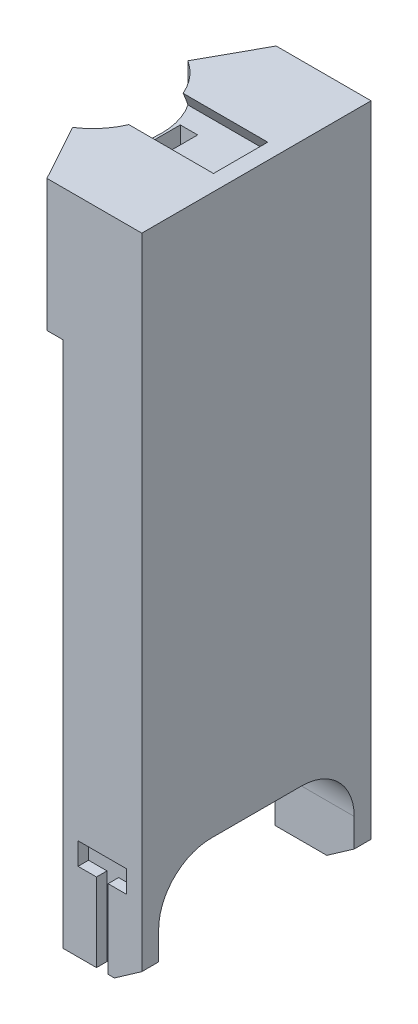
SolidWorks part; units mm, degrees
ref_plane "Front Plane" through (0, 0, 0) normal (0, 0, 1) x (1, 0, 0)
ref_plane "Top Plane" through (0, 0, 0) normal (0, 1, 0) x (1, 0, 0)
ref_plane "Right Plane" through (0, 0, 0) normal (1, 0, 0) x (0, 0, -1)
sketch "Sketch2" plane through (0, 0, 0) normal (0, 1, 0) x (1, 0, 0)
  line L0 (-9, 21.75) -> (-14.9513, 10.9504)
  line L1 (-9, -21.75) -> (9, -21.75)
  line L2 (-9, -21.75) -> (-9, 21.75)
  line L3 (-9, 21.75) -> (9, 21.75)
  line L4 (9, -21.75) -> (9, 21.75)
  line L5 (-9, -21.75) -> (9, 21.75) construction
  line L6 (-9, 21.75) -> (9, -21.75) construction
  line L7 (-9, -21.75) -> (-14.9513, -10.9504)
  circle A0 centre (-22.05, 0) radius 13.05
  point P0 (0, 0)
  point P8 (0, 0)
  point P11 (-27.9421, 0)
  point P12 (-15.3434, 15.5108)
  point P13 (-16.5401, 11.8298)
  point P14 (0, 0)
  point P15 (-14.9513, 10.9504)
  dimension "D1" = 26.1
  dimension "D2" = 43.5
  dimension "D3" = 18
extrude "Boss-Extrude1" add sketch "Sketch2" along normal blind 25 contours A0 L2 L0 | A0 L7 L2 | L1 L4 L3 L2 region at (-10.8717, 0, -12.2283) region at (0, 0, 0) region at (-10.8717, 0, 12.2283)
ref_plane "Plane1" through (-9, 0, 0) normal (1, 0, 0) x (0, 0, -1)
sketch "Sketch3" plane through (-9, 0, 0) normal (1, 0, 0) x (0, 0, -1)
  line L0 (-5.15, 25) -> (5.15, 25)
  line L1 (5.15, 25) -> (7.15, 21.5359)
  line L2 (7.15, 21.5359) -> (-7.15, 21.5359)
  line L3 (-7.15, 21.5359) -> (-5.15, 25)
  line L4 (-21.75, 25) -> (21.75, 25) construction
  point P4 (0, 25)
  point P7 (0, 25)
  point P8 (0, 21.5359)
  dimension "D1" = 10.3
  dimension "D2" = 14.3
  dimension "D3" = 60
extrude "Cut-Extrude1" cut sketch "Sketch3" against normal through all and the other way blind 15
sketch "Sketch4" plane through (-9, 0, 0) normal (1, 0, 0) x (0, 0, -1)
  line L0 (0, 29.4041) -> (0, 4.5359) construction
  line L1 (3.15, 29.4041) -> (3.15, 4.5359)
  line L2 (-3.15, 29.4041) -> (-3.15, 4.5359)
  line L3 (7.15, 21.5359) -> (-7.15, 21.5359) construction
  arc A0 (3.15, 29.4041) -> (-3.15, 29.4041) centre (0, 29.4041) ccw
  arc A1 (-3.15, 4.5359) -> (3.15, 4.5359) centre (0, 4.5359) ccw
  point P3 (0, 16.97)
  dimension "D1" = 6.3
  dimension "D2" = 17
extrude "Cut-Extrude2" cut sketch "Sketch4" along normal blind 3.3 from offset 0.4
sketch "Sketch5" plane through (0, 0, 0) normal (0, -1, 0) x (1, 0, 0)
  line L0 (-9, -21.75) -> (9, -21.75) construction
  line L1 (9, 21.75) -> (-6, 21.75)
  line L2 (9, 21.75) -> (9, -21.75)
  line L3 (9, -21.75) -> (-6, -21.75)
  line L4 (-6, 21.75) -> (-6, -21.75)
  dimension "D1" = 15
extrude "Boss-Extrude2" add sketch "Sketch5" along normal blind 100
sketch "Sketch6" plane through (0, 0, 21.75) normal (0, 0, 1) x (1, 0, 0)
  line L1 (0.4, -85.1) -> (2.6, -85.1)
  line L2 (0.4, -85.1) -> (0.4, -100)
  line L3 (0.4, -100) -> (2.6, -100)
  line L4 (2.6, -85.1) -> (2.6, -100)
  line L5 (0.4, -85.1) -> (2.6, -100) construction
  line L6 (0.4, -100) -> (2.6, -85.1) construction
  line L7 (9, -100) -> (-6, -100) construction
  line L8 (-3.1, -80.9) -> (6.1, -80.9)
  line L9 (-3.1, -80.9) -> (-3.1, -85.1)
  line L10 (-3.1, -85.1) -> (6.1, -85.1)
  line L11 (6.1, -80.9) -> (6.1, -85.1)
  line L12 (-3.1, -80.9) -> (6.1, -85.1) construction
  line L13 (-3.1, -85.1) -> (6.1, -80.9) construction
  point P0 (1.5, -92.55)
  point P5 (3.7214, -119.0502)
  point P7 (1.5, -83)
  point P12 (0, 0)
  point P13 (0, 0)
  point P15 (1.5, -100)
  point P16 (3.5684, -120)
  line M11 (-6, -100) -> (9, -100)
  dimension "D1" = 2.2
  dimension "D2" = 4.2
  dimension "D3" = 9.2
  dimension "D4" = 14.9
extrude "Cut-Extrude3" cut sketch "Sketch6" against normal blind 2 contours L11 L8 L9 L10 L1 | L4 L1 L2 M11 region at (1.5, -83, 21.75) region at (1.5, -92.55, 21.75)
extrude "Cut-Extrude4" cut sketch "Sketch6<3>" along normal blind 2 from surface contours L11 L8 L9 L10 L1 | L4 L1 L2 M11 region at (1.5, -83, 21.75) region at (1.5, -92.55, 21.75) starting at face at (-2, -25, -21.75)
sketch "Sketch6<3>" plane through (0, 0, 21.75) normal (0, 0, 1) x (1, 0, 0) same geometry as "Sketch6"
sketch "Sketch7" plane through (0, 0, 21.75) normal (0, 0, 1) x (1, 0, 0)
  line L0 (9, -100) -> (2.6, -100) construction
  line L1 (9, 25) -> (9, -100) construction
  line L2 (2.6, -85.1) -> (2.6, -100) construction
  line L3 (2.6, -85.1) -> (6.1, -85.1) construction
  line L4 (3.8, -100) -> (9, -96.3589)
  line L5 (9, -96.3589) -> (9, -100)
  line L6 (9, -100) -> (3.8, -100)
  ellipse E0 centre (9, -100) end of major axis (9, -113.7) minor radius 5.2
  line M3 (2.6, -100) -> (9, -100)
  line M4 (9, -100) -> (9, 25)
  dimension "D1" = 1.2
  dimension "D2" = 1.2
  dimension "D3" = 35
extrude "Cut-Extrude5" cut sketch "Sketch7" against normal through all contours L4 M3 M4 region at (7.2667, -98.7863, 21.75)
sketch "Sketch8" plane through (-6, 0, 0) normal (-1, 0, 0) x (0, 0, 1)
  line L0 (21.75, -100) -> (-21.75, -100) construction
  line L1 (18.55, -81) -> (-18.55, -81)
  line L2 (18.55, -81) -> (18.55, -119)
  line L3 (18.55, -119) -> (-18.55, -119)
  line L4 (-18.55, -81) -> (-18.55, -119)
  line L5 (18.55, -81) -> (-18.55, -119) construction
  line L6 (18.55, -119) -> (-18.55, -81) construction
  line L7 (-21.75, -100) -> (-21.75, 0) construction
  point P0 (0, -100)
  point P7 (-15.2199, -101.2827)
  dimension "D1" = 3.2
  dimension "D2" = 19
extrude "Cut-Extrude6" cut sketch "Sketch8" against normal through all
fillet "Fillet1" radius 10 2 edges at (1.5, -81, 18.55) (1.5, -81, -18.55)
